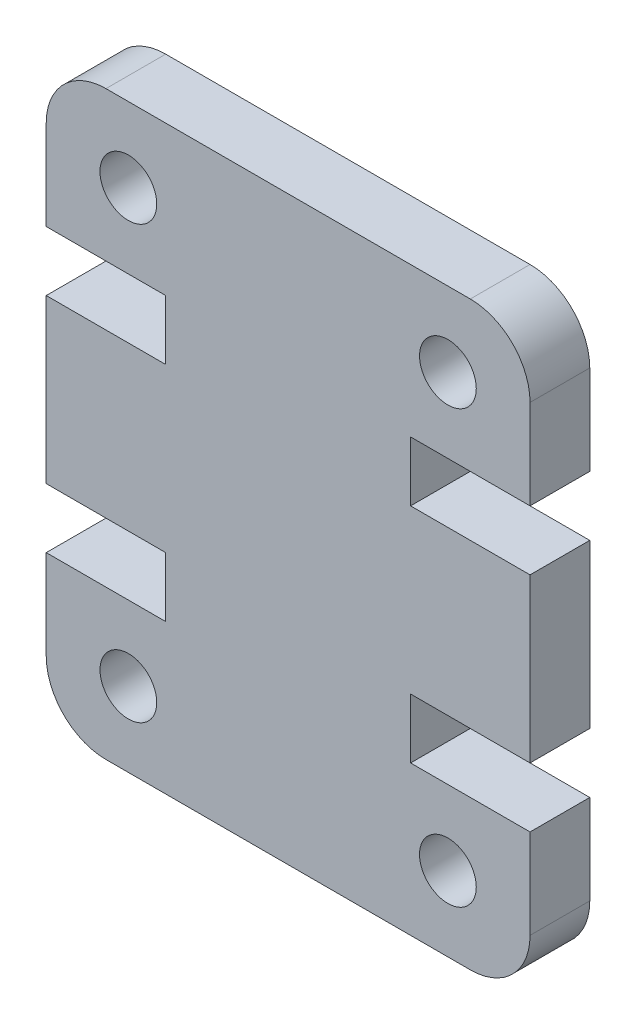
SolidWorks part; units mm, degrees
ref_plane "Front Plane" through (0, 0, 0) normal (0, 0, 1) x (1, 0, 0)
ref_plane "Top Plane" through (0, 0, 0) normal (0, 1, 0) x (1, 0, 0)
ref_plane "Right Plane" through (0, 0, 0) normal (1, 0, 0) x (0, 0, -1)
sketch "Sketch2" plane through (0, 0, 0) normal (0, 0, 1) x (1, 0, 0)
  line L0 (0, 7) -> (0, 12.455)
  line L1 (2, 0) -> (14.2, 0)
  line L2 (16.2, 5) -> (16.2, 2)
  line L3 (0, 9.7275) -> (16.2, 9.7275) construction
  line L4 (12.2, 5) -> (16.2, 5)
  line L5 (16.2, 7) -> (12.2, 7)
  line L6 (12.2, 7) -> (12.2, 5)
  line L7 (16.2, 7) -> (16.2, 12.455)
  line L8 (4, 7) -> (4, 5)
  line L9 (0, 14.455) -> (0, 17.455)
  line L10 (0, 7) -> (4, 7)
  line L11 (4, 5) -> (0, 5)
  line L12 (4, 14.455) -> (0, 14.455)
  line L13 (0, 12.455) -> (4, 12.455)
  line L14 (4, 12.455) -> (4, 14.455)
  line L15 (12.2, 12.455) -> (12.2, 14.455)
  line L16 (16.2, 12.455) -> (12.2, 12.455)
  line L17 (12.2, 14.455) -> (16.2, 14.455)
  line L18 (16.2, 14.455) -> (16.2, 17.455)
  line L19 (0, 5) -> (0, 2)
  line L20 (8.1, 19.455) -> (8.1, 0) construction
  line L21 (2, 19.455) -> (14.2, 19.455)
  circle A0 centre (13.45, 2.5) radius 0.95
  arc A1 (16.2, 2) -> (14.2, 0) centre (14.2, 2) cw
  circle A2 centre (2.75, 16.955) radius 0.95
  arc A3 (0, 2) -> (2, 0) centre (2, 2) ccw
  arc A4 (0, 17.455) -> (2, 19.455) centre (2, 17.455) cw
  circle A5 centre (2.75, 2.5) radius 0.95
  arc A6 (16.2, 17.455) -> (14.2, 19.455) centre (14.2, 17.455) ccw
  circle A7 centre (13.45, 16.955) radius 0.95
  point P18 (8.1, 9.7275)
  dimension "D1" = 1.9
  dimension "D2" = 2
  dimension "D3" = 2.75
  dimension "D4" = 8.1
  dimension "D5" = 2.5
  dimension "D8" = 9.7275
  dimension "D6" = 5
extrude "Boss-Extrude1" add sketch "Sketch2" along normal blind 4
sketch "Sketch3" plane through (0, 0, 4) normal (0, 0, 1) x (1, 0, 0)
  line L0 (0, 0) -> (16.2, 0)
  line L1 (16.2, 0) -> (16.2, 19.455)
  line L2 (16.2, 19.455) -> (0, 19.455)
  line L3 (0, 19.455) -> (0, 0)
extrude "Cut-Extrude1" cut sketch "Sketch3" against normal blind 2
equation "\"D4@Sketch2\"= \"fingerWidth@parametersSketch@prostheticParameters.SLDPRT\" / 2'Finger Width"
equation "\"D8@Sketch2\"= ( ( \"HL@parametersSketch@prostheticParameters.SLDPRT\" * 0.143 ) - 3 - 4 ) / 2 'MIP Length -SiliconeDIP-SiliconeMIP"
equation "\"D1@Sketch2\"= 1.5 + \"tol1@parametersSketch@prostheticParameters.SLDPRT\""
